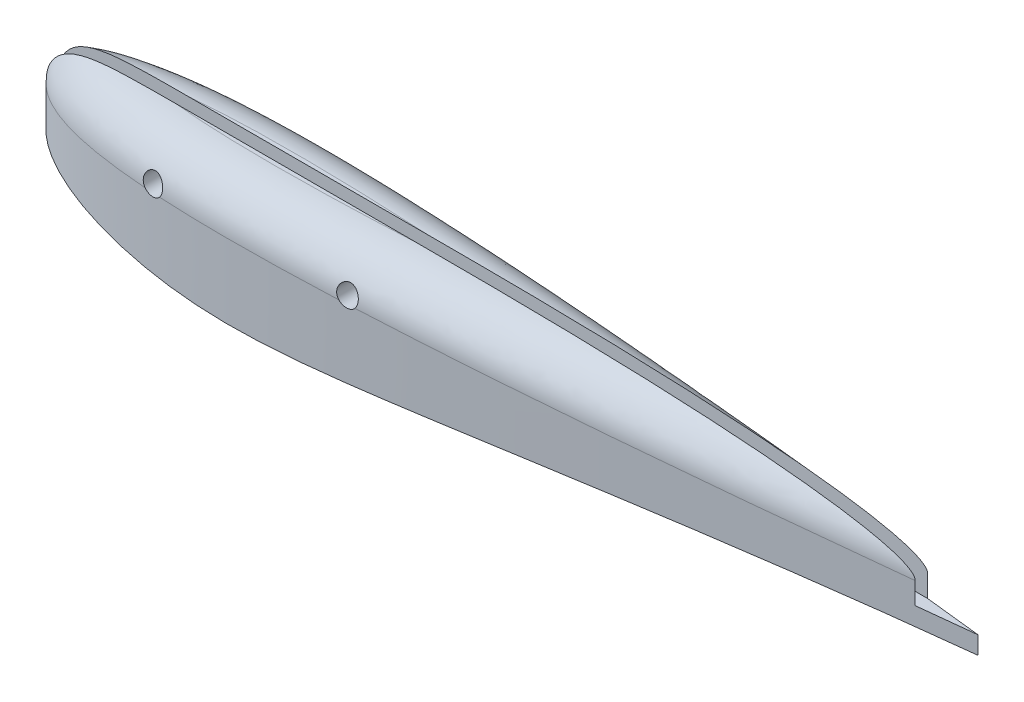
SolidWorks part; units mm, degrees
ref_plane "Front Plane" through (0, 0, 0) normal (0, 0, 1) x (1, 0, 0)
ref_plane "Top Plane" through (0, 0, 0) normal (0, 1, 0) x (1, 0, 0)
ref_plane "Right Plane" through (0, 0, 0) normal (1, 0, 0) x (0, 0, -1)
sketch "Sketch1" plane through (0, 0, 0) normal (0, 1, 0) x (1, 0, 0)
  line L0 (-69.4173, 0) -> (80.5827, 0) construction
  line L1 (-69.4173, 0) -> (-64.1024, 8.4389) construction
  line L2 (-64.1024, 8.4389) -> (-45.4887, 11.5065) construction
  line L3 (-45.4887, 11.5065) -> (-0.5962, 9) construction
  line L4 (-0.5962, 9) -> (80.5827, 0) construction
  line L5 (-69.4173, 0) -> (-64.1024, -8.4389) construction
  line L6 (-64.1024, -8.4389) -> (-45.4887, -11.5065) construction
  line L7 (-45.4887, -11.5065) -> (-0.5962, -9) construction
  line L8 (-0.5962, -9) -> (80.5827, 0) construction
  spline S0 degree 4 poles (-69.4173, 0) (-64.1024, 8.4389) (-45.4887, 11.5065) (-0.5962, 9) (80.5827, 0) knots 0 0 0 0 0 1 1 1 1 1
  spline S1 degree 4 poles (-69.4173, 0) (-64.1024, -8.4389) (-45.4887, -11.5065) (-0.5962, -9) (80.5827, 0) knots 0 0 0 0 0 1 1 1 1 1
  point P6 (-50.3936, 13.7701)
  point P7 (-66.6084, 7.6998)
  point P11 (-64.1024, 8.4389)
  point P12 (-45.4887, 11.5065)
  dimension "D1" = 150
  dimension "D2" = 9
extrude "Boss-Extrude1" add sketch "Sketch1" along normal blind 20
sketch "Sketch2" plane through (0, 0, 0) normal (1, 0, 0) x (0, 0, -1)
  circle A0 centre (0, -2.9003) radius 9.525
  point P2 (0, -2.9003)
  dimension "D1" = 19.05
extrude "Cut-Extrude1" cut sketch "Sketch2" against normal blind 80 and the other way blind 100
fillet "Fillet1" radius 7 2 edges
sketch "Sketch3" plane through (0, 0, 0) normal (1, 0, 0) x (0, 0, -1)
  line L1 (-1, 30.5) -> (1, 30.5)
  line L2 (-1, 30.5) -> (-1, 9.5)
  line L3 (-1, 9.5) -> (1, 9.5)
  line L4 (1, 30.5) -> (1, 9.5)
  line L5 (-1, 30.5) -> (1, 9.5) construction
  line L6 (-1, 9.5) -> (1, 30.5) construction
  point P0 (0, 20)
  dimension "D1" = 2
  dimension "D2" = 21
extrude "Cut-Extrude2" cut sketch "Sketch3" against normal blind 80 and the other way blind 90
ref_plane "Plane1" through (0, 0, 10) normal (0, 0, 1) x (1, 0, 0)
sketch "Sketch4" plane through (0, 0, 10) normal (0, 0, 1) x (1, 0, 0)
  circle A0 centre (-44.2879, 14.0935) radius 1.1
  circle A1 centre (-13.0039, 14.0935) radius 1.1
  dimension "D1" = 2.2
  dimension "D2" = 2.2
extrude "Cut-Extrude3" cut sketch "Sketch4" against normal blind 80
sketch "Sketch5" plane through (0, 0, 10) normal (0, 0, 1) x (1, 0, 0)
  circle A0 centre (-44.2879, 14.0935) radius 1.65
  circle A1 centre (-13.0039, 14.0935) radius 1.65
  dimension "D1" = 3.3
  dimension "D2" = 3.3
extrude "Cut-Extrude4" cut sketch "Sketch5" against normal blind 10
